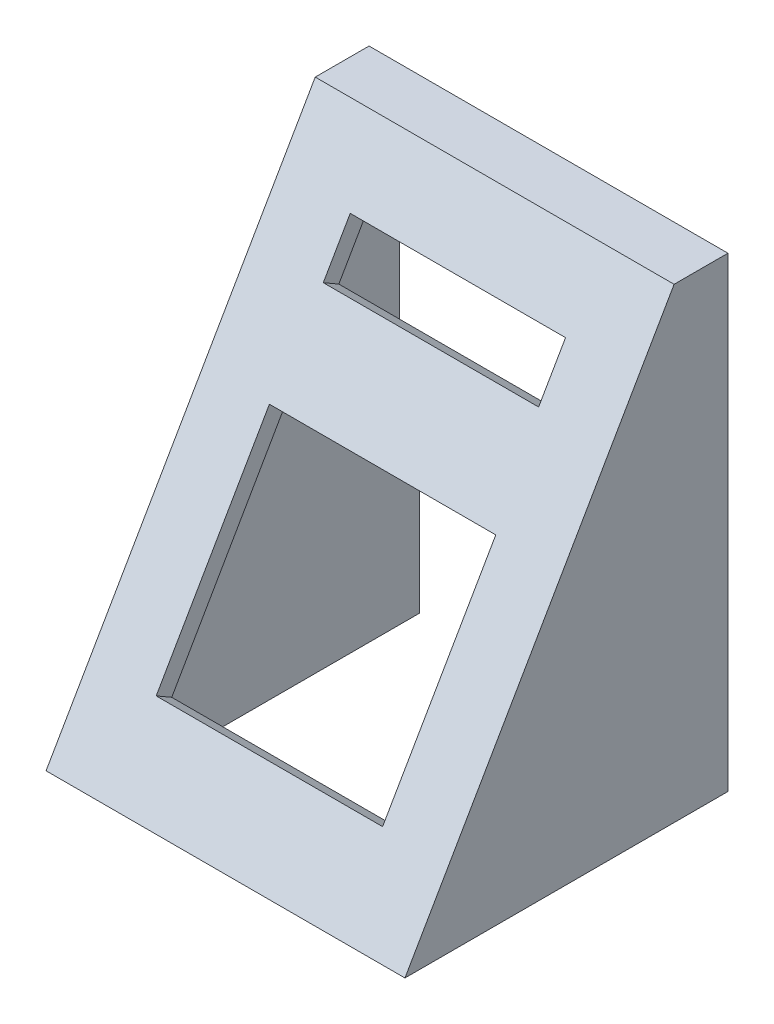
SolidWorks part; units mm, degrees
ref_plane "Front Plane" through (0, 0, 0) normal (0, 0, 1) x (1, 0, 0)
ref_plane "Top Plane" through (0, 0, 0) normal (0, 1, 0) x (1, 0, 0)
ref_plane "Right Plane" through (0, 0, 0) normal (1, 0, 0) x (0, 0, -1)
sketch "Sketch1" plane through (0, 0, 0) normal (1, 0, 0) x (0, 0, -1)
  line L0 (0, 0) -> (0, 129.9038)
  line L1 (0, 129.9038) -> (-75, 0)
  line L2 (-75, 0) -> (0, 0)
  dimension "D1" = 30
  dimension "D2" = 150
extrude "Boss-Extrude1" add sketch "Sketch1" along normal mid plane 100
sketch "Sketch5" plane through (0, 0, 0) normal (1, 0, 0) x (0, 0, -1)
  line L0 (0, 129.9038) -> (15, 129.9038)
  line L1 (15, 129.9038) -> (15, 0)
  line L2 (15, 0) -> (0, 0)
  line L3 (0, 0) -> (0, 129.9038)
  dimension "D1" = 15
extrude "Boss-Extrude2" add sketch "Sketch5" along normal mid plane 100
sketch "Sketch2" plane through (0, 32.476, 56.25) normal (0, 0.5, 0.866) x (1, 0, 0)
  line L1 (-15, -17.5) -> (15, -17.5)
  line L2 (-15, -17.5) -> (-15, -32.5)
  line L3 (-15, -32.5) -> (15, -32.5)
  line L4 (15, -17.5) -> (15, -32.5)
  line L5 (-15, -17.5) -> (15, -32.5) construction
  line L6 (-15, -32.5) -> (15, -17.5) construction
  line L7 (-36, 57.5) -> (36, 57.5)
  line L8 (-36, 57.5) -> (-36, -20.5)
  line L9 (-36, -20.5) -> (36, -20.5)
  line L10 (36, 57.5) -> (36, -20.5)
  line L11 (-36, 57.5) -> (36, -20.5) construction
  line L12 (-36, -20.5) -> (36, 57.5) construction
  line L14 (-40, 102.5) -> (40, 102.5)
  line L15 (-40, 102.5) -> (-40, 66.5)
  line L16 (-40, 66.5) -> (40, 66.5)
  line L17 (40, 102.5) -> (40, 66.5)
  line L18 (-40, 102.5) -> (40, 66.5) construction
  line L19 (-40, 66.5) -> (40, 102.5) construction
  line L20 (50, 112.5) -> (-50, 112.5) construction
  point P0 (0, -25)
  point P6 (0, 18.5)
  point P16 (0, 84.5)
  dimension "D1" = 15
  dimension "D2" = 30
  dimension "D3" = 78
  dimension "D4" = 72
  dimension "D5" = 55
  dimension "D6" = 3
  dimension "D7" = 36
  dimension "D8" = 80
  dimension "D9" = 10
sketch "Sketch3" plane through (0, 32.476, 56.25) normal (0, 0.5, 0.866) x (1, 0, 0)
  line L1 (-31.541, 50.041) -> (31.541, 50.041)
  line L2 (-31.541, 50.041) -> (-31.541, -13.041)
  line L3 (-31.541, -13.041) -> (31.541, -13.041)
  line L4 (31.541, 50.041) -> (31.541, -13.041)
  line L5 (-31.541, 50.041) -> (31.541, -13.041) construction
  line L6 (-31.541, -13.041) -> (31.541, 50.041) construction
  line L9 (-30, 92) -> (30, 92)
  line L10 (-30, 92) -> (-30, 77)
  line L11 (-30, 77) -> (30, 77)
  line L12 (30, 92) -> (30, 77)
  line L13 (-30, 92) -> (30, 77) construction
  line L14 (-30, 77) -> (30, 92) construction
  point P0 (0, 18.5)
  point P5 (0, 84.5)
  dimension "D1" = 63.082
  dimension "D2" = 15
  dimension "D3" = 60
extrude "Cut-Extrude1" cut sketch "Sketch3" against normal through all
sketch "Sketch4" plane through (0, 32.476, 56.25) normal (0, 0.5, 0.866) x (1, 0, 0)
  line L0 (-36, 57.5) -> (36, -20.5) construction
  line L1 (-36, 57.5) -> (36, 57.5)
  line L2 (-36, 57.5) -> (-36, -20.5)
  line L3 (-36, -20.5) -> (-15, -20.5)
  line L4 (36, 57.5) -> (36, -20.5)
  line L5 (-36, 57.5) -> (36, -20.5) construction
  line L6 (-36, -20.5) -> (36, 57.5) construction
  line L7 (-15, -20.5) -> (-15, -32.5)
  line L8 (-37.5, 98) -> (37.5, 98)
  line L9 (-37.5, 98) -> (-37.5, 71)
  line L10 (-37.5, 71) -> (37.5, 71)
  line L11 (37.5, 98) -> (37.5, 71)
  line L12 (-37.5, 98) -> (37.5, 71) construction
  line L13 (-37.5, 71) -> (37.5, 98) construction
  line L14 (-15, -17.5) -> (-15, -32.5) construction
  line L15 (-15, -32.5) -> (15, -32.5)
  line L16 (15, -32.5) -> (15, -20.5)
  line L17 (15, -17.5) -> (15, -32.5) construction
  line L18 (15, -20.5) -> (36, -20.5)
  point P0 (0, 18.5)
  point P8 (0, 84.5)
  dimension "D1" = 27
  dimension "D2" = 75
extrude "Cut-Extrude2" cut sketch "Sketch4" against normal through all from offset 5 offset against normal yes
sketch "Sketch6" plane through (0, 32.476, 56.25) normal (0, 0.5, 0.866) x (1, 0, 0)
  line L0 (-40, 102.5) -> (40, 66.5) construction
  line L1 (-41.5, 104.5) -> (41.5, 104.5)
  line L2 (-41.5, 104.5) -> (-41.5, 64.5)
  line L3 (-41.5, 64.5) -> (41.5, 64.5)
  line L4 (41.5, 104.5) -> (41.5, 64.5)
  line L5 (-41.5, 104.5) -> (41.5, 64.5) construction
  line L6 (-41.5, 64.5) -> (41.5, 104.5) construction
  point P0 (0, 84.5)
  dimension "D1" = 40
  dimension "D2" = 83
extrude "Cut-Extrude3" cut sketch "Sketch6" against normal blind 100 from offset 14 offset against normal yes
sketch "Sketch7" plane through (0, 25.476, 44.1256) normal (0, -0.5, -0.866) x (-1, 0, 0)
  line L0 (40, 102.5) -> (-40, 102.5) construction
  line L1 (40, 102.5) -> (40, 66.5) construction
  line L2 (0, 49.5) -> (0, -49.5) construction
  line L3 (0, 84.5) -> (40, 84.5) construction
  line L4 (40, 102.5) -> (-40, 66.5) construction
  circle A0 centre (37.5, 100) radius 1.5
  circle A1 centre (-37.5, 100) radius 1.5
  circle A2 centre (37.5, 69) radius 1.5
  circle A3 centre (-37.5, 69) radius 1.5
  dimension "D1" = 2.5
  dimension "D3" = 3
  dimension "D2" = 2.5
extrude "Cut-Extrude4" cut sketch "Sketch7" against normal blind 10
